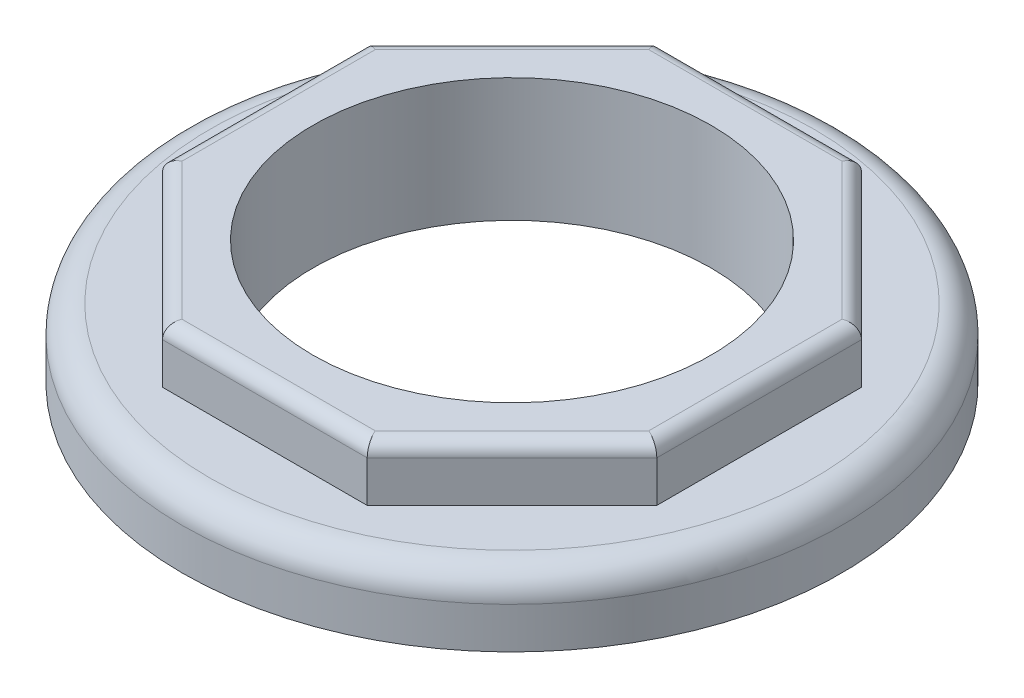
SolidWorks part; units mm, degrees
material "AISI 304"
ref_plane "Alzado" through (0, 0, 0) normal (0, 0, 1) x (1, 0, 0)
ref_plane "Planta" through (0, 0, 0) normal (0, 1, 0) x (1, 0, 0)
ref_plane "Vista lateral" through (0, 0, 0) normal (1, 0, 0) x (0, 0, -1)
sketch "Croquis1" plane through (0, 0, 0) normal (0, 1, 0) x (1, 0, 0)
  line L1 (18, 7.4558) -> (7.4558, 18)
  line L2 (7.4558, 18) -> (-7.4558, 18)
  line L3 (-7.4558, 18) -> (-18, 7.4558)
  line L4 (-18, 7.4558) -> (-18, -7.4558)
  line L5 (-18, -7.4558) -> (-7.4558, -18)
  line L6 (-7.4558, -18) -> (7.4558, -18)
  line L7 (7.4558, -18) -> (18, -7.4558)
  line L8 (18, -7.4558) -> (18, 7.4558)
  circle A0 centre (0, 0) radius 18 construction
  dimension "D1" = 36
extrude "Saliente-Extruir1" add sketch "Croquis1" along normal blind 9
sketch "Croquis2" plane through (0, 9, 0) normal (0, 1, 0) x (1, 0, 0)
  circle A0 centre (0, 0) radius 14.5
  dimension "D1" = 29
extrude "Cortar-Extruir1" cut sketch "Croquis2" against normal through all
fillet "Redondeo1" radius 1 8 edges at (-12.7279, 9, -12.7279) (0, 9, -18) (12.7279, 9, -12.7279) (18, 9, 0) (12.7279, 9, 12.7279) (0, 9, 18) (-12.7279, 9, 12.7279) (-18, 9, 0)
ref_plane "Plano1" through (0, 5, 0) normal (0, 1, 0) x (1, 0, 0)
sketch "Croquis4" plane through (0, 5, 0) normal (0, 1, 0) x (1, 0, 0)
  circle A0 centre (0, 0) radius 24
  dimension "D1" = 48
extrude "Saliente-Extruir2" add sketch "Croquis4" against normal blind 5 contours A0
sketch "Croquis5" plane through (0, 5, 0) normal (0, 1, 0) x (1, 0, 0)
  circle A0 centre (0, 0) radius 14.5
  dimension "D1" = 29
extrude "Cortar-Extruir2" cut sketch "Croquis5" against normal through all
fillet "Redondeo2" radius 2 1 edges at (0, 5, 24) type face fillet first side face at (0, 5, 24) second side face at (0, 0, 24)
shell "Vaciado1" thickness 1 removed face at (0, 0, 14.5)
